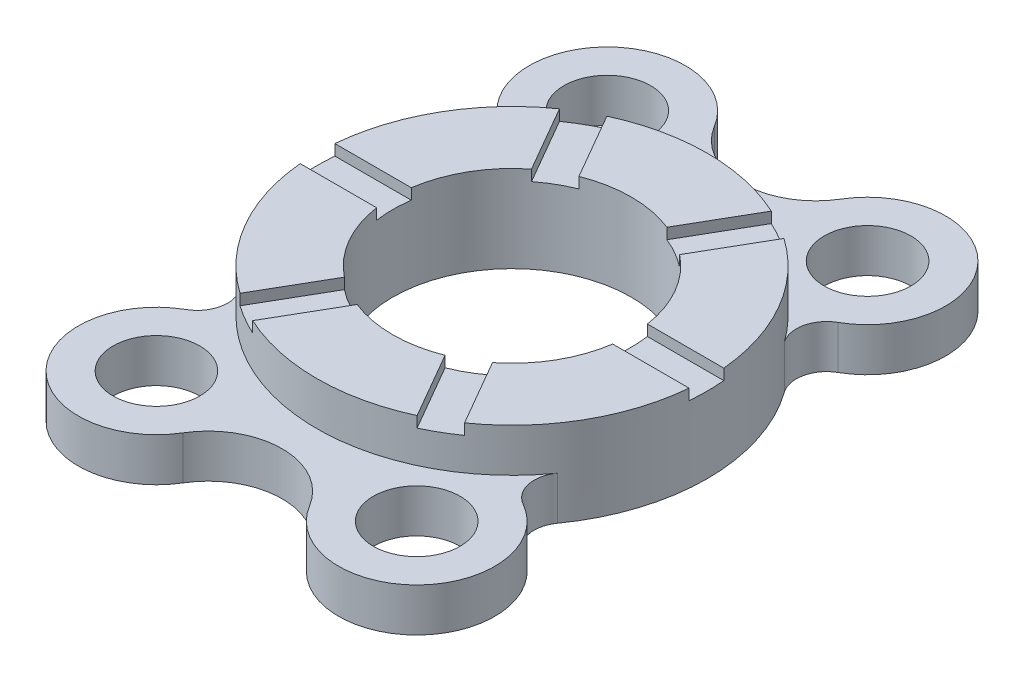
SolidWorks part; units mm, degrees
ref_plane "Спереди" through (0, 0, 0) normal (0, 0, 1) x (1, 0, 0)
ref_plane "Сверху" through (0, 0, 0) normal (0, 1, 0) x (1, 0, 0)
ref_plane "Справа" through (0, 0, 0) normal (1, 0, 0) x (0, 0, -1)
sketch "Эскиз1" plane through (0, 0, 0) normal (0, 1, 0) x (1, 0, 0)
  line L0 (0, -116.5186) -> (0, 116.5186) construction
  line L1 (-126.7582, 0) -> (126.7582, 0) construction
  line L2 (30, -51.9615) -> (0, 0) construction
  line L3 (30, 51.9615) -> (0, 0) construction
  circle A0 centre (0, 0) radius 27.5
  arc A1 (36.6267, -26.1436) -> (36.6267, 26.1436) centre (0, 0) ccw
  circle A2 centre (30, -51.9615) radius 10
  arc A3 (14.5714, -61.2329) -> (38.8734, -36.3007) centre (30, -51.9615) ccw
  arc A4 (36.6267, -26.1436) -> (38.8734, -36.3007) centre (42.3242, -30.2103) ccw
  arc A5 (-36.6267, -26.1436) -> (-38.8734, -36.3007) centre (-42.3242, -30.2103) cw
  circle A6 centre (-30, -51.9615) radius 10
  arc A7 (-14.5714, -61.2329) -> (-38.8734, -36.3007) centre (-30, -51.9615) cw
  arc A8 (14.5714, -61.2329) -> (-14.5714, -61.2329) centre (0, -69.9893) ccw
  arc A9 (-36.6267, 26.1436) -> (-36.6267, -26.1436) centre (0, 0) ccw
  arc A10 (14.5714, 61.2329) -> (-14.5714, 61.2329) centre (0, 69.9893) cw
  arc A11 (-14.5714, 61.2329) -> (-38.8734, 36.3007) centre (-30, 51.9615) ccw
  circle A12 centre (-30, 51.9615) radius 10
  arc A13 (-36.6267, 26.1436) -> (-38.8734, 36.3007) centre (-42.3242, 30.2103) ccw
  arc A14 (36.6267, 26.1436) -> (38.8734, 36.3007) centre (42.3242, 30.2103) cw
  arc A15 (14.5714, 61.2329) -> (38.8734, 36.3007) centre (30, 51.9615) cw
  circle A16 centre (30, 51.9615) radius 10
  point P10 (0, 0)
  point P13 (0, 0)
  dimension "D1" = 55
  dimension "D2" = 90
  dimension "D4" = 20
  dimension "D5" = 36
  dimension "D7" = 14
  dimension "D8" = 34
  dimension "D3" = 60
  dimension "D6" = 30
extrude "Бобышка-Вытянуть1" add sketch "Эскиз1" along normal blind 10
sketch "Эскиз2" plane through (0, 10, 0) normal (0, 1, 0) x (1, 0, 0)
  arc A0 (-36.6267, 26.1436) -> (-36.6267, -26.1436) centre (0, 0) ccw construction
  circle A1 centre (0, 0) radius 27.5 construction
  arc A2 (-36.6267, 26.1436) -> (-36.6267, -26.1436) centre (0, 0) ccw
  circle A3 centre (0, 0) radius 27.5
  circle A4 centre (0, 0) radius 45
  arc M4 (36.6267, -26.1436) -> (36.6267, 26.1436) centre (0, 0) ccw
  arc M10 (-36.6267, 26.1436) -> (-36.6267, -26.1436) centre (0, 0) ccw
  circle M16 centre (0, 0) radius 27.5
extrude "Бобышка-Вытянуть2" add sketch "Эскиз2" along normal blind 10 contours A4 M4 M10 M16 region at (0, 10, -43.7272)
sketch "Эскиз3" plane through (0, 0, 0) normal (1, 0, 0) x (0, 0, -1)
  line L0 (27.5, 20) -> (-27.5, 20) construction
  line L1 (27.5, 20) -> (-27.5, 20) construction
  line L2 (0, 0) -> (0, 20) construction
  line L3 (0, 0) -> (0, 30) construction
  line L4 (4, 20) -> (4, 17.5)
  line L5 (4, 20) -> (-4, 20)
  line L6 (0, 20) -> (0, 17.5) construction
  line L7 (4, 17.5) -> (-4, 17.5)
  line L8 (-4, 20) -> (-4, 17.5)
  dimension "D2" = 5
  dimension "D1" = 8
ref_axis "Ось1" through (0, -50, 0) along (0, 1, 0)
extrude "Вырез-Вытянуть2" cut sketch "Эскиз3" against normal blind 108
pattern_circular "Круговой массив2" count 6 over 360 about axis through (0, -50, 0) along (0, 1, 0) of "Вырез-Вытянуть2"
